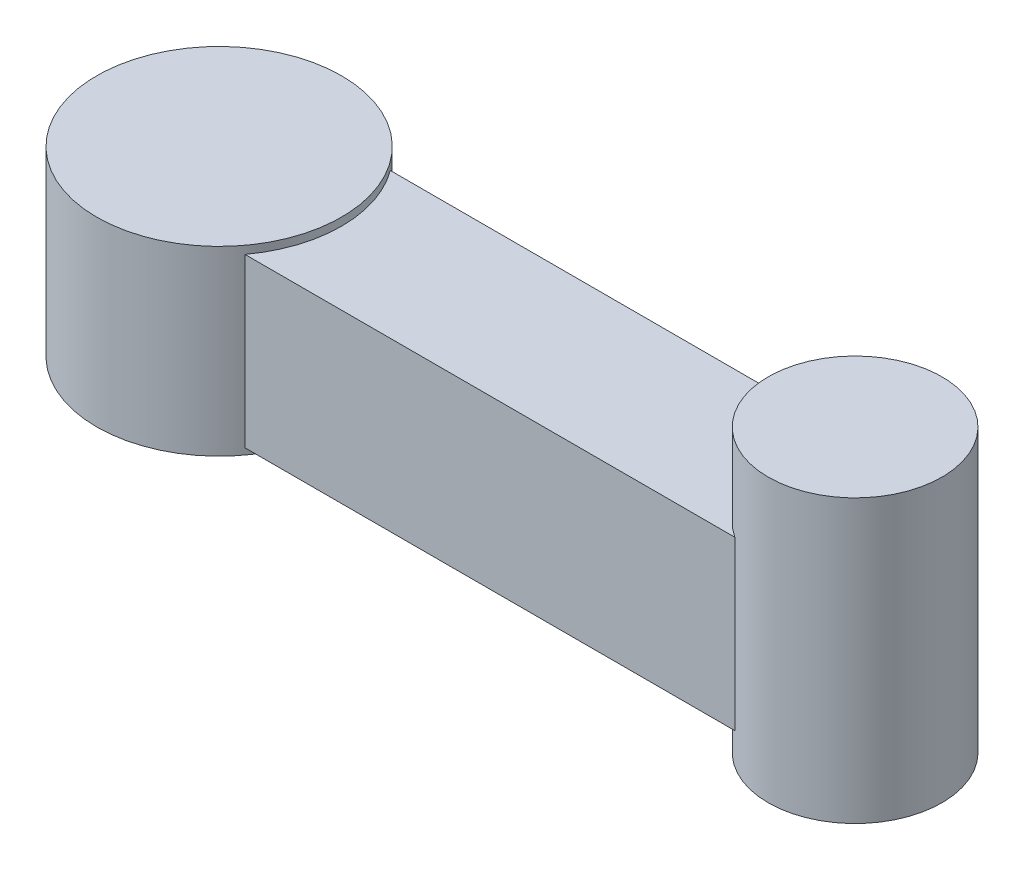
SolidWorks part; units mm, degrees
ref_plane "Alzado" through (0, 0, 0) normal (0, 0, 1) x (1, 0, 0)
ref_plane "Planta" through (0, 0, 0) normal (0, 1, 0) x (1, 0, 0)
ref_plane "Vista lateral" through (0, 0, 0) normal (1, 0, 0) x (0, 0, -1)
sketch "Croquis1" plane through (0, 0, 0) normal (0, 1, 0) x (1, 0, 0)
  line L0 (77.4999, 0.1251) -> (347.4999, 0.1251) construction
  line L1 (62.3719, 46) -> (372.3501, 46)
  line L2 (62.3719, -46) -> (372.3501, -46)
  arc A0 (62.3719, 46) -> (62.3719, -46) centre (0, 0) ccw
  arc A1 (372.3501, -46) -> (372.3501, 46) centre (402.4998, 0) ccw
  dimension "D1" = 155
  dimension "D2" = 110
  dimension "D3" = 270
  dimension "D4" = 92
extrude "Saliente-Extruir1" add sketch "Croquis1" along normal blind 106
sketch "Croquis2" plane through (0, 106, 0) normal (0, 1, 0) x (1, 0, 0)
  circle A0 centre (0, 0) radius 77.5
extrude "Saliente-Extruir2" add sketch "Croquis2" along normal blind 5 and the other way blind 110
sketch "Croquis3" plane through (0, 106, 0) normal (0, 1, 0) x (1, 0, 0)
  circle A0 centre (402.4998, 0) radius 55
extrude "Saliente-Extruir3" add sketch "Croquis3" along normal blind 52.5 and the other way blind 126
